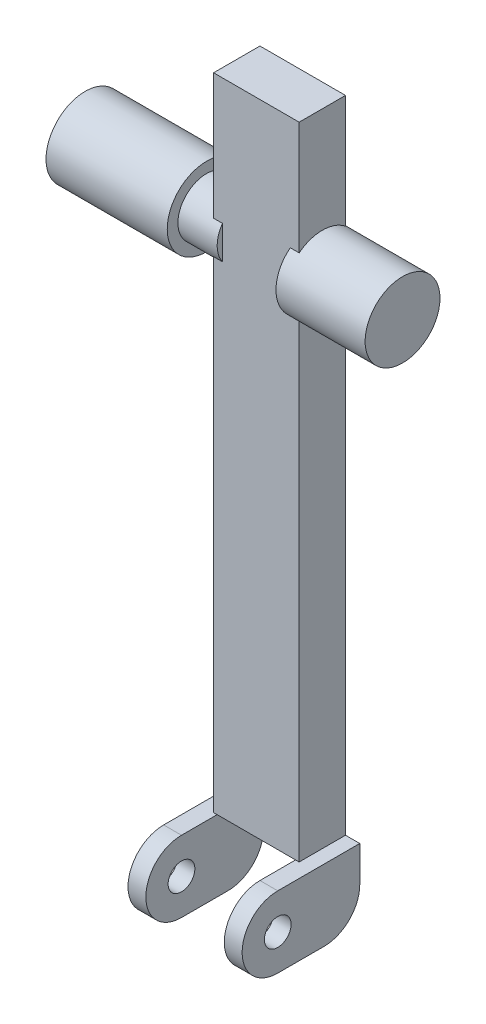
SolidWorks part; units mm, degrees
ref_plane "Front Plane" through (0, 0, 0) normal (0, 0, 1) x (1, 0, 0)
ref_plane "Top Plane" through (0, 0, 0) normal (0, 1, 0) x (1, 0, 0)
ref_plane "Right Plane" through (0, 0, 0) normal (1, 0, 0) x (0, 0, -1)
sketch "Sketch1" plane through (0, 0, 0) normal (0, 1, 0) x (1, 0, 0)
  line L1 (-24, 13) -> (24, 13)
  line L2 (-24, 13) -> (-24, -13)
  line L3 (-24, -13) -> (24, -13)
  line L4 (24, 13) -> (24, -13)
  line L5 (-24, 13) -> (24, -13) construction
  line L6 (-24, -13) -> (24, 13) construction
  point P0 (0, 0)
ref_plane "Plane1" through (19, 0, 0) normal (1, 0, 0) x (0, 0, -1)
sketch "Sketch2" plane through (19, 0, 0) normal (1, 0, 0) x (0, 0, -1)
  line L0 (13, 0) -> (-13, 0) construction
  circle A0 centre (0, 0) radius 21
ref_plane "Plane2" through (-19, 0, 0) normal (1, 0, 0) x (0, 0, -1)
sketch "Sketch3" plane through (-19, 0, 0) normal (1, 0, 0) x (0, 0, -1)
  line L0 (13, 0) -> (-13, 0) construction
  circle A0 centre (0, 0) radius 16
extrude "Boss-Extrude1" add sketch "Sketch3" against normal blind 22
ref_plane "Plane3" through (-41, 0, 0) normal (-1, 0, 0) x (0, 0, 1)
sketch "Sketch4" plane through (-41, 0, 0) normal (-1, 0, 0) x (0, 0, 1)
  circle A0 centre (0, 0) radius 22
extrude "Boss-Extrude2" add sketch "Sketch4" along normal blind 68
extrude "Boss-Extrude3" add sketch "Sketch2" along normal blind 50 separate body
extrude "Boss-Extrude5" add sketch "Sketch1" along normal blind 80 and the other way blind 279.4
ref_plane "Plane4" through (24, 0, 0) normal (1, 0, 0) x (0, 0, -1)
sketch "Sketch5" plane through (24, 0, 0) normal (1, 0, 0) x (0, 0, -1)
  line L1 (13, -279.4) -> (-33, -279.4)
  line L3 (13, -279.4) -> (13, -299.4)
  line L4 (-7, -319.4) -> (-33, -319.4)
  arc A0 (-33, -279.4) -> (-33, -319.4) centre (-33, -299.4) ccw
  arc A1 (-7, -319.4) -> (13, -299.4) centre (-7, -299.4) ccw
  dimension "D1" = 20
  dimension "D2" = 20
extrude "Boss-Extrude7" add sketch "Sketch5" along normal blind 8 and the other way blind 2 separate body
ref_plane "Plane8" through (22, 0, 0) normal (-1, 0, 0) x (0, 0, 1)
sketch "Sketch10" plane through (22, 0, 0) normal (-1, 0, 0) x (0, 0, 1)
  circle A0 centre (33, -299.4) radius 7.5
extrude "Cut-Extrude4" cut sketch "Sketch10" against normal up to vertex (10 mm away) up to point (32, -319.4, 33)
mirror "Mirror26" about plane through (0, 0, 0) normal (1, 0, 0) of "Cut-Extrude4", "Boss-Extrude7"
ref_point "Point1"
ref_point "Point2"
ref_axis "Axis1" through (69, 0, 0) along (-1, 0, 0)
sketch "Sketch11" plane through (-109, 0, 0) normal (-1, 0, 0) x (0, 0, 1)
  line L0 (0, 0) -> (0, 22) construction
  circle A0 centre (0, 0) radius 22 construction
ref_plane "Plane5" through (0, 0, 0) normal (1, 0, 0) x (0, 0, -1)
ref_plane "Plane9" through (0, 0, 0) normal (0, 1, 0) x (1, 0, 0)
ref_plane "Plane10" through (0, 0, 0) normal (0, 0, -1) x (-1, 0, 0)
ref_axis "Axis2" through (0, 0, 52.1997) along (0, 0, -1)
ref_axis "Axis3" through (0, 186.9, 0) along (0, -1, 0)
